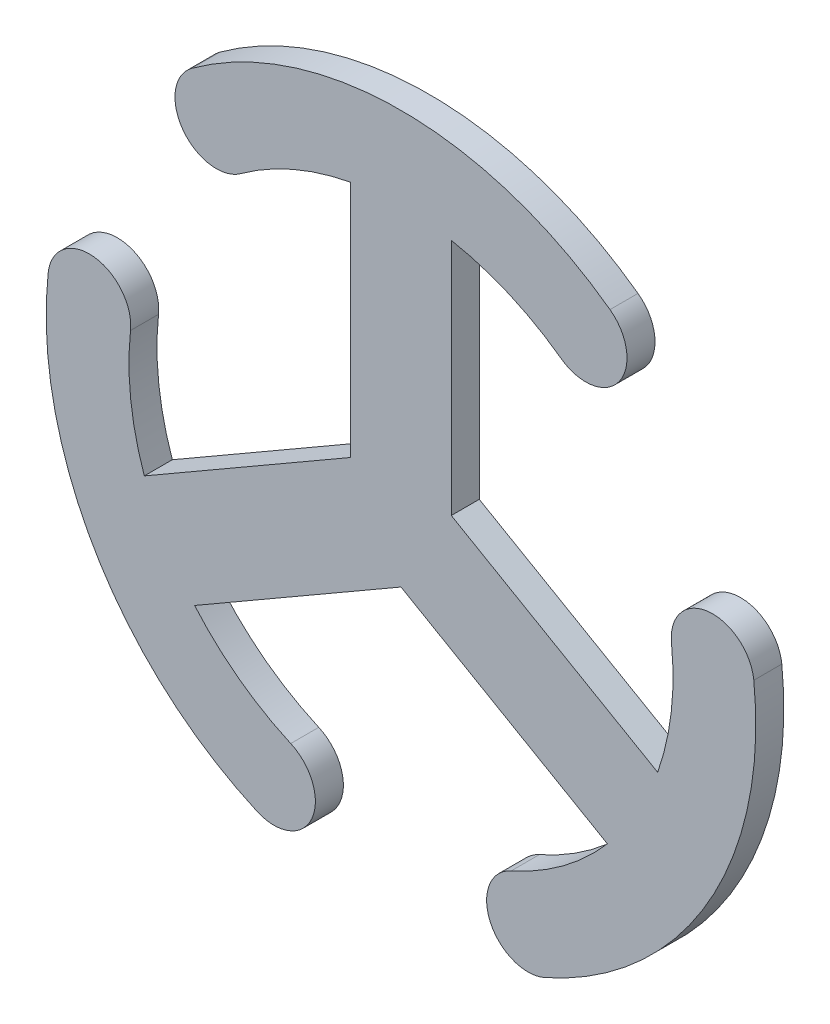
SolidWorks part; units mm, degrees
ref_plane "Front Plane" through (0, 0, 0) normal (0, 0, 1) x (1, 0, 0)
ref_plane "Top Plane" through (0, 0, 0) normal (0, 1, 0) x (1, 0, 0)
ref_plane "Right Plane" through (0, 0, 0) normal (1, 0, 0) x (0, 0, -1)
sketch "Sketch2" plane through (0, 0, 0) normal (0, 0, 1) x (1, 0, 0)
  line L0 (0, 19) -> (-16.4545, -9.5)
  line L1 (-16.4545, -9.5) -> (16.4545, -9.5)
  line L2 (16.4545, -9.5) -> (0, 19)
  line L9 (-2.6919, 0) -> (2.6919, 0)
  line L10 (-2.6919, 0) -> (-2.6919, 19)
  line L11 (-2.6919, 19) -> (2.6919, 19)
  line L12 (2.6919, 0) -> (2.6919, 19)
  circle A5 centre (0, 0) radius 19
  arc A6 (9.8862, 13.5628) -> (-9.8862, 13.5628) centre (0, 0) ccw construction
  arc A7 (11.1917, 15.354) -> (-11.1917, 15.354) centre (0, 0) ccw
  arc A8 (8.5806, 11.7717) -> (-8.5806, 11.7717) centre (0, 0) ccw
  arc A9 (8.5806, 11.7717) -> (11.1917, 15.354) centre (9.8862, 13.5628) ccw
  arc A10 (-11.1917, 15.354) -> (-8.5806, 11.7717) centre (-9.8862, 13.5628) ccw
  point P8 (0, 16.7835)
  point P17 (0, 0)
  point P18 (0, 0)
  point P19 (-8.984, 14.82)
  point P20 (0, 0)
  point P21 (-9.8862, 13.5628)
  dimension "D1" = 38
extrude "Boss-Extrude3" add sketch "Sketch2" along normal blind 1.5 contours L12 A8 L10 L9 | A9 A7 A10 A8 region at (0, 7.242, 0)
sketch "Sketch5" plane through (0, 0, 0) normal (1, 0, 0) x (0, 0, -1)
  line L0 (0, 0) -> (12.727, 0)
pattern_circular "CirPattern1" count 3 over 360 about axis through (0, 0, 0) along (0, 0, -1) of "Boss-Extrude3"
